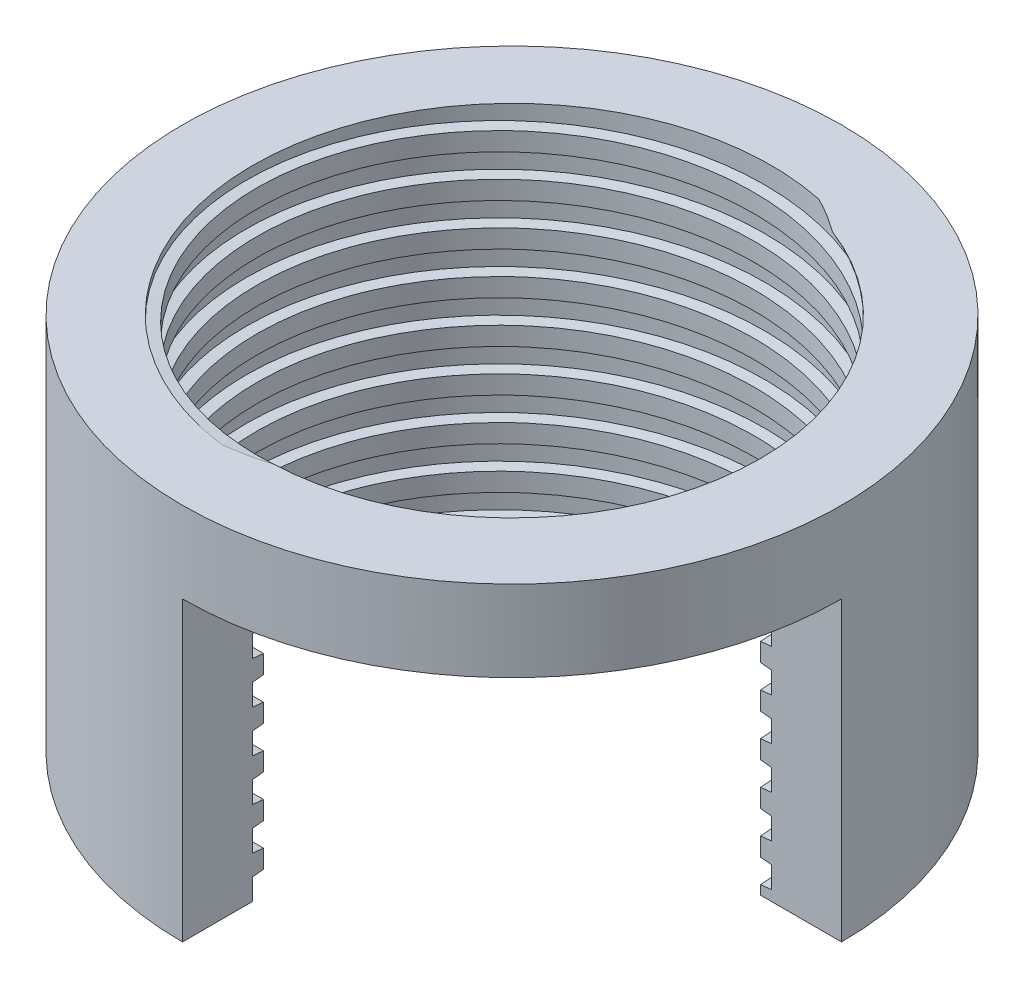
SolidWorks part; units mm, degrees
ref_plane "Front Plane" through (0, 0, 0) normal (0, 0, 1) x (1, 0, 0)
ref_plane "Top Plane" through (0, 0, 0) normal (0, 1, 0) x (1, 0, 0)
ref_plane "Right Plane" through (0, 0, 0) normal (1, 0, 0) x (0, 0, -1)
sketch "Sketch2" plane through (0, 0, 0) normal (0, 1, 0) x (1, 0, 0)
  circle A0 centre (0, 0) radius 4.6
  circle A1 centre (0, 0) radius 6.1
  dimension "D1" = 9.2
  dimension "D2" = 1.5
extrude "Boss-Extrude1" add sketch "Sketch2" along normal blind 7
sketch "Sketch3" plane through (0, 0, 0) normal (0, 0, 1) x (1, 0, 0)
  line L0 (-4.6, 0) -> (-4.8, 0) construction
  line L1 (-4.6, 0) -> (4.6, 0) construction
  line L2 (-4.8, -0.2) -> (-4.8, 0.2)
  line L3 (-4.8, 0.2) -> (-4.6, 0.22)
  line L4 (-4.6, 0.22) -> (-4.6, -0.22)
  line L5 (-4.8, -0.2) -> (-4.6, -0.22)
  dimension "D1" = 4.8
  dimension "D2" = 0.4
  dimension "D3" = 0.44
sketch "Sketch5" plane through (0, 0, 0) normal (0, 1, 0) x (1, 0, 0)
  circle A0 centre (0, 0) radius 4.6 construction
  circle A1 centre (0, 0) radius 4.6
curve "Helix/Spiral1" pitch 0.78 height 7 radius 4.6 centre (0, 0, 0) axis (0, 1, 0) start towards (0, 0, 1)
sweep "Cut-Sweep1" cut profiles "Sketch3" path "Helix/Spiral1" align with end faces yes
sketch "Sketch6" plane through (0, 0, 0) normal (0, 1, 0) x (1, 0, 0)
  line L0 (0, 0) -> (7, 0)
  line L1 (0, 0) -> (0, -7)
  arc A0 (7, 0) -> (0, -7) centre (0, 0) cw
  dimension "D1" = 7
extrude "cutout" cut sketch "Sketch6" along normal blind 5.5
